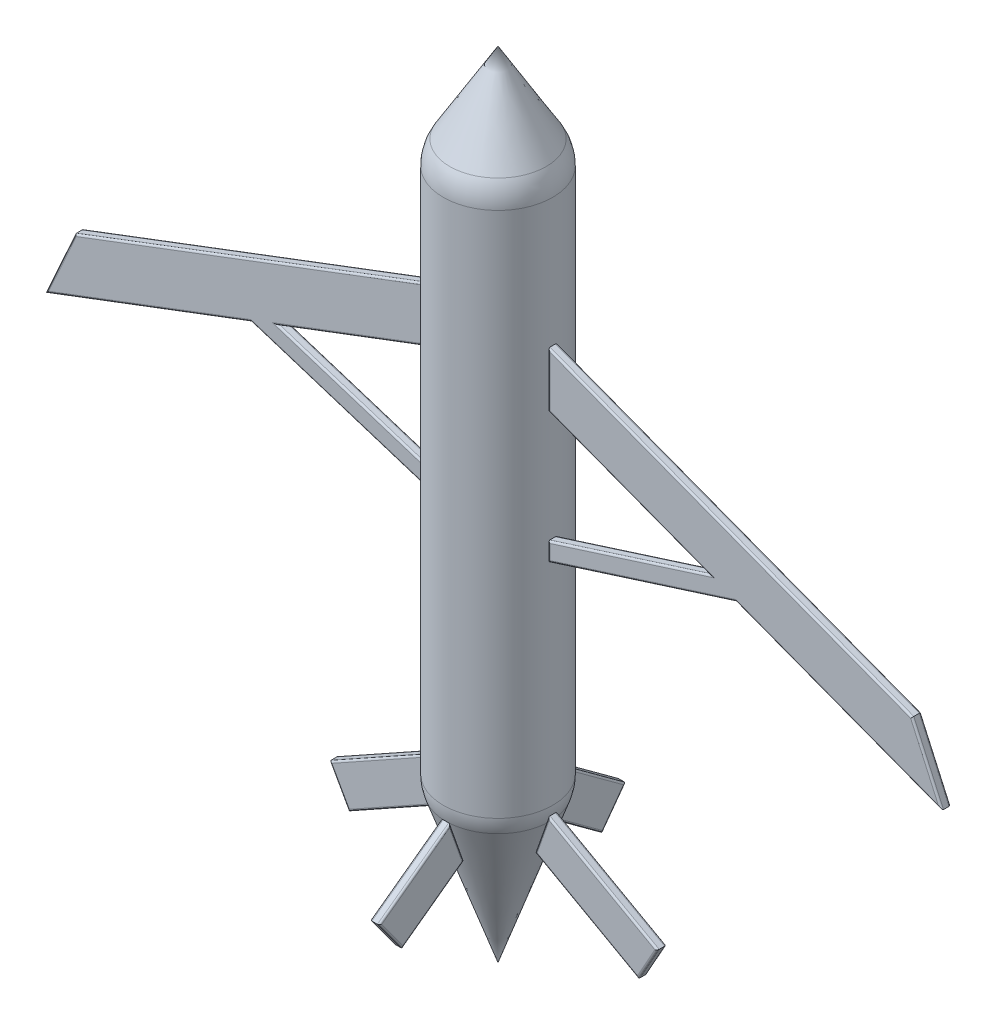
SolidWorks part; units mm, degrees
other "相机1"
ref_plane "前视基准面" through (0, 0, 0) normal (0, 0, 1) x (1, 0, 0)
ref_plane "上视基准面" through (0, 0, 0) normal (0, 1, 0) x (1, 0, 0)
ref_plane "右视基准面" through (0, 0, 0) normal (1, 0, 0) x (0, 0, -1)
sketch "草图2" plane through (0, 0, 0) normal (0, 0, 1) x (1, 0, 0)
  line L0 (0, 0) -> (0, 500)
  line L1 (0, 500) -> (60, 400)
  line L2 (60, 400) -> (60, -200)
  line L3 (60, -200) -> (0, -200)
  line L4 (0, -200) -> (0, 0)
  dimension "D1" = 500
  dimension "D2" = 200
  dimension "D3" = 60
  dimension "D4" = 100
revolve "旋转1" add sketch "草图2" angle 360 about L0
sketch "草图3" plane through (0, 0, 0) normal (0, 0, 1) x (1, 0, 0)
  line L0 (-60, 245.4157) -> (-459.208, 94.1547)
  line L1 (-60, 400) -> (-60, -200) construction
  line L2 (-459.208, 94.1547) -> (-491.7642, 21.8764)
  line L3 (-236.6711, 118.5319) -> (-60, 185.473)
  line L4 (-265.9516, 107.4374) -> (-60, 41.8197)
  line L5 (-60, 41.8197) -> (-60, 62.2431)
  line L6 (-60, 62.2431) -> (-236.6711, 118.5319)
  line L8 (-60, 185.473) -> (-60, 245.4157)
  line L9 (-265.9516, 107.4374) -> (-491.7642, 21.8764)
  line L10 (0, -228.7566) -> (0, 228.7566) construction
  line L11 (265.9516, 107.4374) -> (60, 41.8197)
  line L12 (60, 41.8197) -> (60, 62.2431)
  line L13 (60, 62.2431) -> (236.6711, 118.5319)
  line L14 (236.6711, 118.5319) -> (60, 185.473)
  line L15 (60, 185.473) -> (60, 245.4157)
  line L16 (60, 245.4157) -> (459.208, 94.1547)
  line L17 (459.208, 94.1547) -> (491.7642, 21.8764)
  line L18 (265.9516, 107.4374) -> (491.7642, 21.8764)
extrude "凸台-拉伸1" add sketch "草图3" along normal blind 5 and the other way blind 5 separate body
sketch "草图5" plane through (0, 0, 0) normal (0, 0, 1) x (1, 0, 0)
  line L0 (0, -200) -> (0, -370.7713)
  line L1 (-60, -200) -> (60, -200) construction
  line L2 (0, -370.7713) -> (-60, -200)
  line L3 (-60, 400) -> (-60, -200) construction
  line L4 (-60, -200) -> (0, -200)
revolve "旋转2" add sketch "草图5" angle 360 about L0
sketch "草图6" plane through (0, 0, 0) normal (0, 0, 1) x (1, 0, 0)
  line L0 (-60, -200) -> (-179.8262, -266.8533)
  line L1 (-179.8262, -266.8533) -> (-158.8609, -304.431)
  line L2 (-158.8609, -304.431) -> (-45.525, -241.1987)
  line L3 (-60, -200) -> (0, -370.7713) construction
  line L4 (-45.525, -241.1987) -> (-60, -200)
  line L5 (0, -228.7566) -> (0, 228.7566) construction
  line L6 (158.8609, -304.431) -> (45.525, -241.1987)
  line L7 (179.8262, -266.8533) -> (158.8609, -304.431)
  line L8 (60, -200) -> (179.8262, -266.8533)
  line L9 (45.525, -241.1987) -> (60, -200)
extrude "凸台-拉伸2" add sketch "草图6" along normal blind 5 and the other way blind 5 separate body
fillet "圆角1" radius 2 16 edges at (-148.3356, 152.0025, 5) (-148.3356, 90.3875, 5) (-60, 52.0314, 5) (-162.9758, 74.6285, 5) (-378.8579, 64.6569, 5) (-475.4861, 58.0156, 5) (-259.604, 169.7852, 5) (-60, 215.4444, 5) (-259.604, 169.7852, -5) (-475.4861, 58.0156, -5) (-378.8579, 64.6569, -5) (-162.9758, 74.6285, -5) (-60, 52.0314, -5) (-148.3356, 90.3875, -5) (-148.3356, 152.0025, -5) (-60, 215.4444, -5)
fillet "圆角2" radius 2 16 edges at (475.4861, 58.0156, -5) (259.604, 169.7852, -5) (60, 215.4444, -5) (148.3356, 152.0025, -5) (148.3356, 90.3875, -5) (60, 52.0314, -5) (162.9758, 74.6285, -5) (378.8579, 64.6569, -5) (162.9758, 74.6285, 5) (60, 52.0314, 5) (148.3356, 90.3875, 5) (148.3356, 152.0025, 5) (60, 215.4444, 5) (259.604, 169.7852, 5) (475.4861, 58.0156, 5) (378.8579, 64.6569, 5)
fillet "圆角3" radius 2 8 edges at (102.1929, -272.8149, 5) (52.7625, -220.5994, 5) (119.9131, -233.4267, 5) (169.3435, -285.6422, 5) (119.9131, -233.4267, -5) (52.7625, -220.5994, -5) (102.1929, -272.8149, -5) (169.3435, -285.6422, -5)
fillet "圆角4" radius 2 8 edges at (-119.9131, -233.4267, -5) (-169.3435, -285.6422, -5) (-102.1929, -272.8149, -5) (-52.7625, -220.5994, -5) (-102.1929, -272.8149, 5) (-169.3435, -285.6422, 5) (-119.9131, -233.4267, 5) (-52.7625, -220.5994, 5)
fillet "圆角5" radius 50 1 edges at (0, 400, -60)
fillet "圆角6" radius 50 1 edges at (0, -200, -60)
sketch "草图7" plane through (0, 0, 0) normal (1, 0, 0) x (0, 0, -1)
  line L0 (-57.1731, -208.046) -> (-135.3658, -265.2655)
  line L1 (-135.3658, -265.2655) -> (-109.756, -300.2623)
  line L2 (-109.756, -300.2623) -> (-42.1541, -250.7929)
  line L3 (-57.1731, -208.046) -> (0, -370.7713) construction
  line L4 (-42.1541, -250.7929) -> (-57.1731, -208.046)
  line L5 (0, 393.0939) -> (0, -393.0939) construction
  line L6 (109.756, -300.2623) -> (42.1541, -250.7929)
  line L7 (135.3658, -265.2655) -> (109.756, -300.2623)
  line L8 (57.1731, -208.046) -> (135.3658, -265.2655)
  line L9 (42.1541, -250.7929) -> (57.1731, -208.046)
extrude "凸台-拉伸3" add sketch "草图7" along normal blind 5 and the other way blind 5 separate body
fillet "圆角7" radius 2 8 edges at (5, -275.5276, 75.955) (5, -282.7639, 122.5609) (5, -236.6557, 96.2695) (5, -229.4194, 49.6636) (-5, -236.6557, 96.2695) (-5, -282.7639, 122.5609) (-5, -275.5276, 75.955) (-5, -229.4194, 49.6636)
fillet "圆角8" radius 2 8 edges at (-5, -236.6557, -96.2695) (-5, -229.4194, -49.6636) (-5, -275.5276, -75.955) (-5, -282.7639, -122.5609) (5, -275.5276, -75.955) (5, -229.4194, -49.6636) (5, -236.6557, -96.2695) (5, -282.7639, -122.5609)
